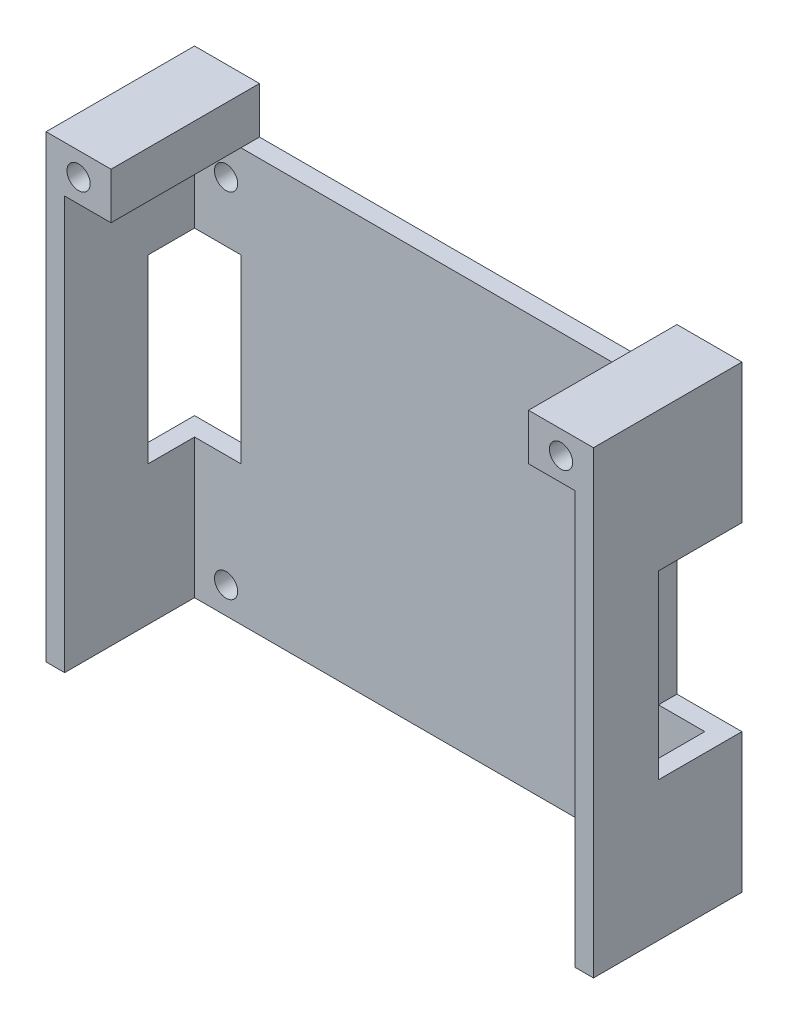
SolidWorks part; units mm, degrees
ref_plane "Front Plane" through (0, 0, 0) normal (0, 0, 1) x (1, 0, 0)
ref_plane "Top Plane" through (0, 0, 0) normal (0, 1, 0) x (1, 0, 0)
ref_plane "Right Plane" through (0, 0, 0) normal (1, 0, 0) x (0, 0, -1)
sketch "Sketch1" plane through (0, 0, 0) normal (0, 1, 0) x (1, 0, 0)
  line L0 (0, 0) -> (2, 0)
  line L1 (0, 0) -> (59, 0) construction
  line L2 (0, 0) -> (0, 9)
  line L3 (0, 9) -> (59, 9)
  line L4 (59, 0) -> (59, 9)
  line L5 (2, 0) -> (2, 7)
  line L6 (2, 7) -> (57, 7)
  line L7 (57, 7) -> (57, 0)
  line L8 (57, 0) -> (59, 0)
  dimension "D1" = 59
  dimension "D2" = 9
  dimension "D3" = 2
  dimension "D4" = 7
  dimension "D5" = 55
extrude "Boss-Extrude1" add sketch "Sketch1" along normal blind 44.5
sketch "Sketch3" plane through (0, 0, -9) normal (0, 0, -1) x (-1, 0, 0)
  line L0 (-59, 0) -> (-59, 8) construction
  line L1 (-59, 44.5) -> (-59, 0) construction
  line L2 (-59, 8) -> (-59, 2)
  line L3 (-59, 5) -> (-59.5, 5) construction
  line L4 (-59, 8) -> (-59.5, 8)
  line L5 (-59, 2) -> (-59.5, 2)
  line L6 (0, 0) -> (0, 8) construction
  line L7 (0, 44.5) -> (0, 0) construction
  line L8 (0, 8) -> (0.5, 8)
  line L9 (0, 8) -> (0, 2)
  line L10 (0, 2) -> (0.5, 2)
  line L11 (0, 5) -> (0.5, 5) construction
  arc A0 (-59.5, 8) -> (-59.5, 2) centre (-59.5, 5) ccw
  circle A1 centre (-59.5, 5) radius 1.25
  arc A2 (0.5, 8) -> (0.5, 2) centre (0.5, 5) cw
  circle A3 centre (0.5, 5) radius 1.25
  dimension "D4" = 3
  dimension "D5" = 2.5
  dimension "D11" = 3
  dimension "D12" = 2.5
  dimension "D1" = 8
  dimension "D2" = 6
  dimension "D3" = 0.5
  dimension "D6" = 8
  dimension "D7" = 0.5
  dimension "D8" = 6
  dimension "D9" = 0.5
sketch "Sketch4" plane through (0, 44.5, 0) normal (0, 1, 0) x (1, 0, 0)
  line L0 (59, 9) -> (0, 9) construction
  line L1 (0, 0) -> (7, 0)
  line L2 (0, 0) -> (0, 9)
  line L3 (0, 9) -> (7, 9)
  line L4 (7, 0) -> (7, 9)
  line L6 (59, 0) -> (52, 0)
  line L7 (59, 0) -> (59, 9)
  line L8 (59, 9) -> (52, 9)
  line L9 (52, 0) -> (52, 9)
  dimension "D1" = 7
  dimension "D2" = 7
extrude "Boss-Extrude3" add sketch "Sketch4" along normal blind 5
sketch "Sketch5" plane through (0, 0, -9) normal (0, 0, -1) x (-1, 0, 0)
  line L0 (-59, 49.5) -> (-52, 44.5) construction
  line L1 (0, 49.5) -> (-7, 44.5) construction
  circle A0 centre (-55.5, 47) radius 1.25
  circle A1 centre (-3.5, 47) radius 1.25
  dimension "D1" = 2.5
  dimension "D2" = 2.5
extrude "Cut-Extrude3" cut sketch "Sketch5" against normal through all
sketch "Sketch7" plane through (0, 0, -9) normal (0, 0, -1) x (-1, 0, 0)
  line L0 (-59, 0) -> (-59, 2.9) construction
  line L1 (-59, 49.5) -> (-59, 0) construction
  line L2 (-59, 2.9) -> (0, 2.9) construction
  line L3 (0, 49.5) -> (0, 0) construction
  line L4 (-53.6, 2.9) -> (-5.4, 2.9)
  line L5 (-53.6, 2.9) -> (-53.6, 40.95) construction
  line L6 (-53.6, 40.95) -> (-5.4, 40.95) construction
  circle A0 centre (-53.6, 2.9) radius 1.25
  circle A1 centre (-5.4, 2.9) radius 1.25
  circle A2 centre (-53.6, 40.95) radius 1.25
  circle A3 centre (-5.4, 40.95) radius 1.25
  point P11 (-29.5, 2.9)
  dimension "D3" = 2.5
  dimension "D4" = 2.5
  dimension "D6" = 2.5
  dimension "D8" = 2.5
  dimension "D1" = 2.9
  dimension "D2" = 48.2
  dimension "D5" = 38.05
  dimension "D7" = 48.2
extrude "Cut-Extrude4" cut sketch "Sketch7" against normal blind 10 contours A2 | A3 | A1 | A0 region at (5.4, 4.1146, -9) region at (54.8146, 2.9, -9) region at (53.6, 40.95, -9) region at (5.4, 40.95, -9)
extrude "Boss-Extrude4" add sketch "Sketch3" against normal blind 3 contours L9 A3 | L2 A1 region at (58.6906, 5, -9) region at (0.3094, 5, -9)
mirror "Mirror2" about plane through (0, 0, 0) normal (0, 0, 1) of bodies 110
chamfer "Chamfer1" [suppressed] distance 4 angle 45
sketch "Sketch10" plane through (0, 0, -9) normal (0, 0, -1) x (-1, 0, 0)
  line L0 (-59, 49.5) -> (-59, 0) construction
  line L1 (-59, 15) -> (-52, 15)
  line L2 (-59, 15) -> (-59, 34.5)
  line L3 (-59, 34.5) -> (-52, 34.5)
  line L4 (-52, 15) -> (-52, 34.5)
  line L5 (-29.5, -2.6848) -> (-29.5, 49.4375) construction
  line L6 (-52, 44.5) -> (-7, 44.5) construction
  line L7 (-7, 15) -> (-7, 34.5)
  line L8 (0, 34.5) -> (-7, 34.5)
  line L9 (0, 15) -> (0, 34.5)
  line L10 (0, 15) -> (-7, 15)
  line L11 (-59, 49.5) -> (-52, 49.5) construction
  line L12 (-59, 0) -> (0, 0) construction
  point P10 (-29.5, 44.5)
  point P15 (-52.356, 29.5196)
  dimension "D1" = 15
  dimension "D2" = 15
  dimension "D3" = 7
extrude "Cut-Extrude6" cut sketch "Sketch10" against normal blind 7
chamfer "Chamfer3" distance 2 angle 45 2 edges at (0, 24.75, -2) (59, 24.75, -2)
sketch "Sketch9" plane through (0, 0, 0) normal (0, -1, 0) x (1, 0, 0)
  line L0 (59, 9) -> (59, -9) construction
  line L1 (0, 9) -> (59, 9)
  line L2 (0, 9) -> (0, 7)
  line L3 (0, 7) -> (59, 7)
  line L4 (59, 9) -> (59, 7)
  line L6 (2, 7) -> (57, 7) construction
extrude "Cut-Extrude5" cut sketch "Sketch9" against normal through all both and the other way through all
sketch "Sketch11" plane through (0, 0, -9) normal (0, 0, -1) x (-1, 0, 0)
  line L0 (-32.1436, 39.3669) -> (-24.5688, 39.3669)
  line L1 (-24.5688, 39.3669) -> (-28.2931, 29.3067)
  line L2 (-28.2931, 29.3067) -> (-20.7184, 29.3067)
  line L3 (-20.7184, 29.3067) -> (-37.5139, 7.1449)
  line L4 (-37.5139, 7.1449) -> (-33.0312, 22.2645)
  line L5 (-33.0312, 22.2645) -> (-40.606, 22.2645)
  line L6 (-40.606, 22.2645) -> (-32.1436, 39.3669)
  point P6 (-32.1436, 39.3669)
extrude "Cut-Extrude7" cut sketch "Sketch11" against normal blind 0.5
